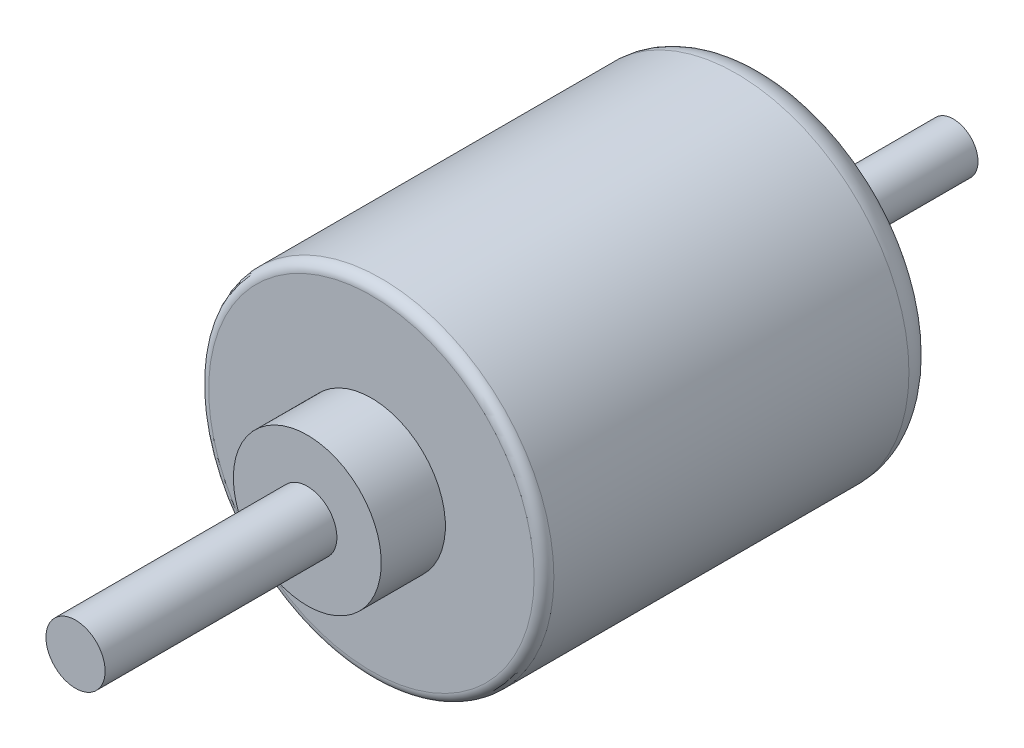
SolidWorks part; units mm, degrees
ref_plane "Front Plane" through (0, 0, 0) normal (0, 0, 1) x (1, 0, 0)
ref_plane "Top Plane" through (0, 0, 0) normal (0, 1, 0) x (1, 0, 0)
ref_plane "Right Plane" through (0, 0, 0) normal (1, 0, 0) x (0, 0, -1)
sketch "Sketch1" plane through (0, 0, 0) normal (0, 0, 1) x (1, 0, 0)
  circle A0 centre (0, 0) radius 17.5
  circle A1 centre (0, 0) radius 5.5
  circle A3 centre (0, 0) radius 2.5
  circle A4 centre (0, 0) radius 3
  circle A5 centre (0, 0) radius 7.5
extrude "Boss-Extrude2" add sketch "Sketch1" along normal blind 40 contours A0
extrude "Boss-Extrude3" add sketch "Sketch1<3>" against normal blind 19 contours A3
sketch "Sketch1<3>" plane through (0, 0, 0) normal (0, 0, 1) x (1, 0, 0) same geometry as "Sketch1"
extrude "Boss-Extrude4" add sketch "Sketch1<4>" along normal blind 42 contours A1
sketch "Sketch1<4>" plane through (0, 0, 0) normal (0, 0, 1) x (1, 0, 0) same geometry as "Sketch1"
extrude "Boss-Extrude5" add sketch "Sketch1<5>" along normal blind 70 contours A4
sketch "Sketch1<5>" plane through (0, 0, 0) normal (0, 0, 1) x (1, 0, 0) same geometry as "Sketch1"
extrude "Boss-Extrude6" add sketch "Sketch1<6>" along normal blind 46.5 contours A5
sketch "Sketch1<6>" plane through (0, 0, 0) normal (0, 0, 1) x (1, 0, 0) same geometry as "Sketch1"
fillet "Fillet1" radius 1 1 edges at (17.5, 0, 40)
fillet "Fillet2" radius 3 1 edges at (17.5, 0, 0)
sketch "Sketch2" plane through (0, 0, 40) normal (0, 0, 1) x (1, 0, 0)
  circle A0 centre (0, 0) radius 14.5
